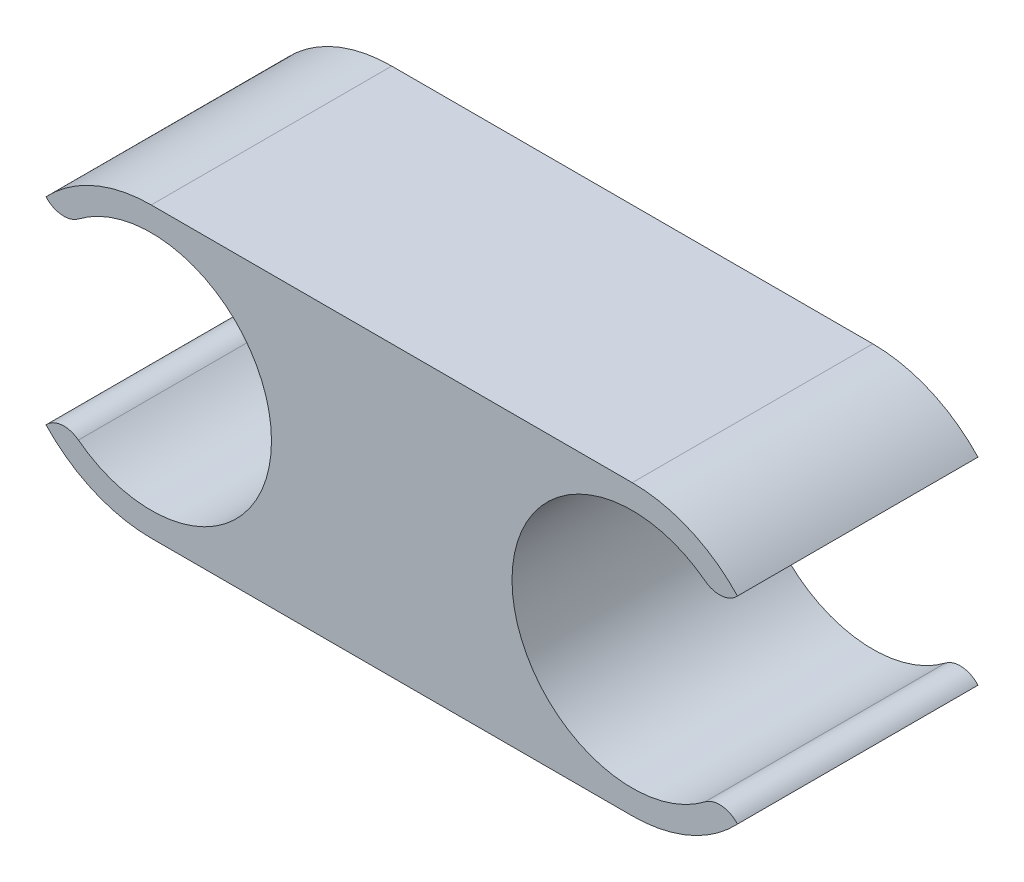
SolidWorks part; units mm, degrees
ref_plane "前视基准面" through (0, 0, 0) normal (0, 0, 1) x (1, 0, 0)
ref_plane "上视基准面" through (0, 0, 0) normal (0, 1, 0) x (1, 0, 0)
ref_plane "右视基准面" through (0, 0, 0) normal (1, 0, 0) x (0, 0, -1)
sketch "草图1" plane through (0, 0, 0) normal (0, 0, 1) x (1, 0, 0)
  line L1 (-41.4711, -12.5893) -> (-25.4711, -12.5893)
  line L2 (-41.4711, -12.5893) -> (-41.4711, -22.1893)
  line L3 (-41.4711, -22.1893) -> (-25.4711, -22.1893)
  line L4 (-25.4711, -12.5893) -> (-25.4711, -22.1893)
  line L5 (-41.4711, -22.1893) -> (-44.9711, -22.1893)
  line L6 (-41.4711, -22.1893) -> (-41.4711, -12.5893)
  line L7 (-41.4711, -12.5893) -> (-44.9711, -12.5893)
  line L8 (-44.9711, -22.1893) -> (-44.9711, -12.5893)
  line L9 (-25.4711, -12.5893) -> (-21.9711, -12.5893)
  line L10 (-25.4711, -12.5893) -> (-25.4711, -22.1893)
  line L11 (-25.4711, -22.1893) -> (-21.9711, -22.1893)
  line L12 (-21.9711, -12.5893) -> (-21.9711, -22.1893)
  circle A0 centre (-41.4711, -17.3893) radius 4
  circle A1 centre (-25.4711, -17.3893) radius 4
  circle A2 centre (-41.4711, -17.3893) radius 4.8
  circle A3 centre (-25.4711, -17.3893) radius 4.8
extrude "凸台-拉伸1" add sketch "草图1" along normal blind 8 contours A3 L1 A2 L3 | L2 A2 A0 | L4 A3 A1 | L12 A3 L4 A1 | L4 A3 L12 A1 | L2 A2 L8 A0 | L8 A2 L2 A0 region at (-38.1528, -14.0711, 0) region at (-33.4711, -17.3893, 0) region at (-43.3599, -13.5975, 0) region at (-23.5823, -13.5975, 0) region at (-25.5784, -12.9893, 0) region at (-23.5823, -21.1811, 0) region at (-43.3599, -21.1811, 0)
fillet "圆角1" radius 0.8 4 edges at (-21.9711, -19.3258, 4) (-21.9711, -15.4528, 4) (-44.9711, -19.3258, 4) (-44.9711, -15.4528, 4)
